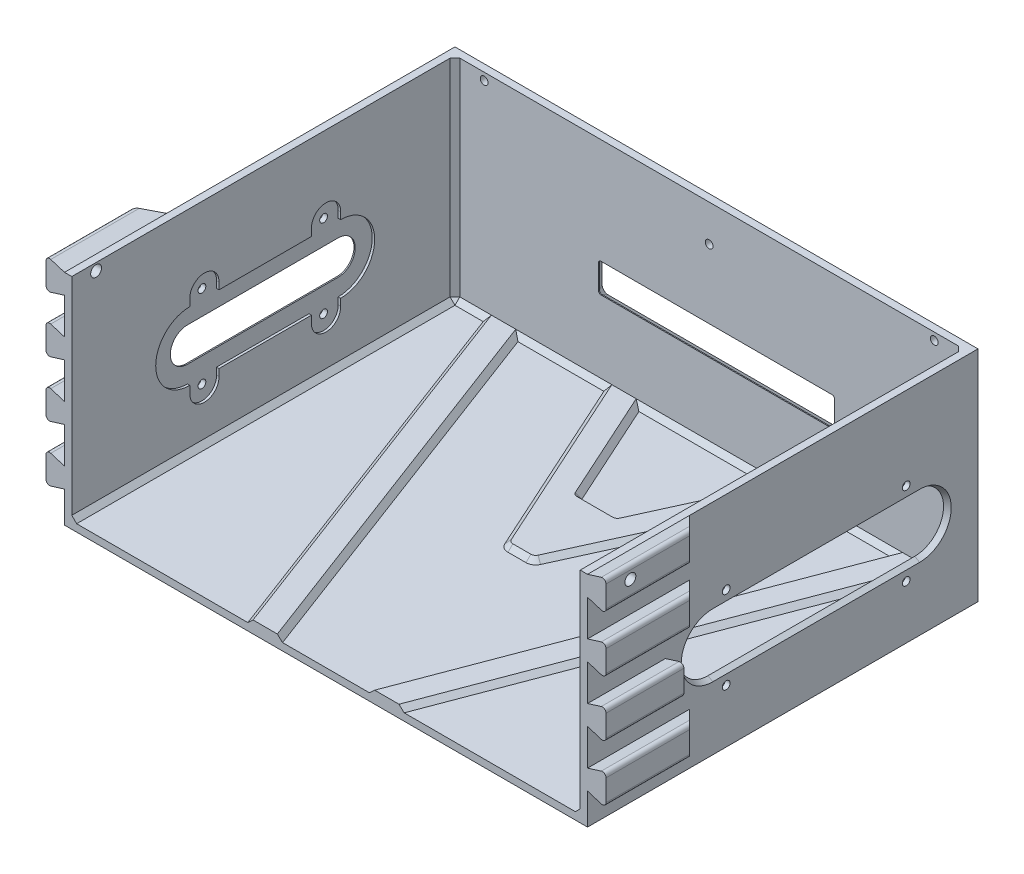
SolidWorks part; units mm, degrees
ref_plane "Płaszczyzna przednia" through (0, 0, 0) normal (0, 0, 1) x (1, 0, 0)
ref_plane "Płaszczyzna górna" through (0, 0, 0) normal (0, 1, 0) x (1, 0, 0)
ref_plane "Płaszczyzna prawa" through (0, 0, 0) normal (1, 0, 0) x (0, 0, -1)
sketch "Szkic1" plane through (0, 0, 0) normal (0, 0, 1) x (1, 0, 0)
  line L1 (0, 0) -> (215, 0)
  line L2 (0, 0) -> (0, 90)
  line L3 (0, 90) -> (215, 90)
  line L4 (215, 0) -> (215, 90)
  dimension "D1" = 90
  dimension "D2" = 215
extrude "Dodanie-wyciągnięcie1" add sketch "Szkic1" along normal blind 3
sketch "Szkic2" plane through (0, 0, 3) normal (0, 0, 1) x (1, 0, 0)
  line L0 (0, 90) -> (0, 0)
  line L1 (0, 0) -> (215, 0)
  line L2 (215, 0) -> (215, 90)
  line L3 (215, 90) -> (212, 90)
  line L4 (215, 90) -> (0, 90) construction
  line L5 (212, 90) -> (212, 3)
  line L6 (212, 3) -> (3, 3)
  line L7 (3, 3) -> (3, 90)
  line L8 (3, 90) -> (0, 90)
  dimension "D1" = 3
  dimension "D2" = 3
  dimension "D3" = 3
extrude "Dodanie-wyciągnięcie2" add sketch "Szkic2" along normal blind 157.5
sketch "Szkic3" plane through (0, 3, 0) normal (0, 1, 0) x (1, 0, 0)
  line L0 (18, -3) -> (77.5, -160.5)
  line L1 (212, -3) -> (3, -3) construction
  line L2 (212, -160.5) -> (3, -160.5) construction
  line L3 (28, -3) -> (87.5, -160.5)
  line L4 (212, -3) -> (3, -3) construction
  line L5 (100.1515, -50) -> (114.8485, -50)
  line L6 (77.5, -160.5) -> (87.5, -160.5)
  line L7 (18, -3) -> (28, -3)
  line L8 (197, -3) -> (137.5, -160.5)
  line L9 (137.5, -160.5) -> (127.5, -160.5)
  line L10 (127.5, -160.5) -> (137.5, -160.5)
  line L11 (127.5, -160.5) -> (187, -3)
  line L12 (187, -3) -> (197, -3)
  line L13 (215, 0) -> (0, 0) construction
  line L14 (67.5, -3) -> (101.9671, -78.8276)
  line L15 (113.0329, -78.8276) -> (147.5, -3)
  line L16 (137.5, -3) -> (116.6693, -48.8276)
  line L17 (98.3307, -48.8276) -> (77.5, -3)
  line L18 (103.7878, -80) -> (111.2122, -80)
  line L19 (67.5, -3) -> (77.5, -3)
  line L20 (137.5, -3) -> (147.5, -3)
  line L21 (107.5, 0) -> (107.5, -100) construction
  arc A0 (114.8485, -50) -> (116.6693, -48.8276) centre (114.8485, -48) ccw
  arc A1 (100.1515, -50) -> (98.3307, -48.8276) centre (100.1515, -48) cw
  arc A2 (111.2122, -80) -> (113.0329, -78.8276) centre (111.2122, -78) ccw
  arc A3 (103.7878, -80) -> (101.9671, -78.8276) centre (103.7878, -78) cw
  point P14 (107.5, 0)
  point P33 (112.5, -80)
  point P36 (102.5, -80)
  point P39 (107.5, -50)
  line M5 (212, -3) -> (3, -3)
  line M7 (3, -160.5) -> (212, -160.5)
  dimension "D16" = 2
  dimension "D1" = 20
  dimension "D2" = 15
  dimension "D3" = 40
  dimension "D4" = 10
  dimension "D5" = 15
  dimension "D6" = 10
  dimension "D7" = 10
  dimension "D8" = 10
  dimension "D9" = 10
  dimension "D10" = 10
  dimension "D11" = 10
  dimension "D12" = 5
  dimension "D13" = 60
  dimension "D14" = 80
  dimension "D15" = 30
extrude "Dodanie-wyciągnięcie3" add sketch "Szkic3" along normal blind 2 contours L3 L0 M5 M7 | L11 L8 M7 M5 | L20 L15 A2 L18 A3 L14 L19 L17 A1 L5 A0 L16 region at (52.75, 3, 81.75) region at (162.25, 3, 81.75)
chamfer "Sfazowanie2" distance 2 angle 45 23 edges at (167.25, 3, 81.75) (212, 46.5, 3) (212, 3, 81.75) (204.5, 3, 3) (57.75, 3, 81.75) (157.25, 3, 81.75) (167.25, 3, 3) (47.75, 3, 3) (47.75, 3, 81.75) (10.5, 3, 3) (3, 3, 81.75) (3, 46.5, 3) (107.5, 3, 3) (84.7335, 3, 40.9138) (102.7051, 3, 79.6815) (107.5, 3, 80) (112.2949, 3, 79.6815) (130.2665, 3, 40.9138) (127.0846, 3, 25.9138) (115.9313, 3, 49.6815) (107.5, 3, 50) (99.0687, 3, 49.6815) (87.9154, 3, 25.9138)
sketch "Szkic4" plane through (0, 0, 3) normal (0, 0, 1) x (1, 0, 0)
  line L0 (184.1065, 3) -> (148.7878, 3) construction
  line L1 (63, 46.7) -> (158, 46.7)
  line L2 (62, 45.7) -> (62, 35.7)
  line L3 (63, 34.7) -> (158, 34.7)
  line L4 (159, 45.7) -> (159, 35.7)
  line L5 (212, 90) -> (212, 5) construction
  arc A0 (158, 46.7) -> (159, 45.7) centre (158, 45.7) cw
  arc A1 (158, 34.7) -> (159, 35.7) centre (158, 35.7) ccw
  arc A2 (62, 35.7) -> (63, 34.7) centre (63, 35.7) ccw
  arc A3 (63, 46.7) -> (62, 45.7) centre (63, 45.7) ccw
  point P12 (159, 34.7)
  point P15 (62, 34.7)
  point P18 (62, 46.7)
  dimension "D5" = 1
  dimension "D1" = 31.7
  dimension "D2" = 53
  dimension "D3" = 12
  dimension "D4" = 97
extrude "Wytnij-wyciągnięcie1" cut sketch "Szkic4" against normal blind 10
sketch "Szkic5" plane through (215, 0, 0) normal (1, 0, 0) x (0, 0, -1)
  line L0 (-109, 39) -> (-24, 39) construction
  line L1 (-109, 50.5) -> (-24, 50.5)
  line L2 (-109, 27.5) -> (-24, 27.5)
  line L3 (-160.5, 0) -> (0, 0) construction
  line L4 (-160.5, 90) -> (0, 90) construction
  line L5 (0, 0) -> (0, 90) construction
  arc A0 (-109, 50.5) -> (-109, 27.5) centre (-109, 39) ccw
  arc A1 (-24, 27.5) -> (-24, 50.5) centre (-24, 39) ccw
  point P2 (-66.5, 39)
  dimension "D4" = 24
  dimension "D1" = 27.5
  dimension "D2" = 39.5
  dimension "D3" = 85
extrude "Wytnij-wyciągnięcie2" cut sketch "Szkic5" against normal blind 10
chamfer "Sfazowanie4" distance 1.5 angle 60 12 edges at (110.5, 46.7, 0) (158.7071, 46.4071, 0) (62.2929, 46.4071, 0) (159, 40.7, 0) (62, 40.7, 0) (158.7071, 34.9929, 0) (62.2929, 34.9929, 0) (110.5, 34.7, 0) (215, 39, 12.5) (215, 50.5, 66.5) (215, 27.5, 66.5) (215, 39, 120.5) first distance on face at (110.5, 40.7, 0) first distance on face at (215, 39, 66.5)
sketch "Szkic6" plane through (215, 0, 0) normal (1, 0, 0) x (0, 0, -1)
  line L0 (-24, 39) -> (-109, 39) construction
  line L1 (-24, 24) -> (-109, 24)
  line L2 (-24, 54) -> (-109, 54)
  line L3 (-66.5, 39) -> (-66.5, 64.1072) construction
  line L4 (-109, 54) -> (-98, 54)
  line L5 (-109, 54) -> (-109, 56)
  line L7 (-98, 54) -> (-98, 56)
  line L8 (-66.5, 39) -> (-84.4826, 39) construction
  line L9 (-35, 54) -> (-35, 56)
  line L10 (-24, 54) -> (-24, 56)
  line L11 (-24, 54) -> (-35, 54)
  line L12 (-109, 54) -> (-109, 56)
  line L13 (-98, 54) -> (-98, 56)
  line L14 (-35, 54) -> (-35, 56)
  line L15 (-24, 54) -> (-24, 56)
  line L16 (-109, 54) -> (-109, 56)
  line L17 (-98, 54) -> (-98, 56)
  line L18 (-35, 54) -> (-35, 56)
  line L19 (-24, 54) -> (-24, 56)
  line L20 (-109, 54) -> (-109, 56)
  line L21 (-98, 54) -> (-98, 56)
  line L22 (-35, 54) -> (-35, 56)
  line L23 (-24, 54) -> (-24, 56)
  line L24 (-66.5, 39) -> (-132.3508, 39) construction
  line L25 (-109, 54) -> (-109, 56)
  line L26 (-98, 54) -> (-98, 56)
  line L27 (-35, 54) -> (-35, 56)
  line L28 (-24, 54) -> (-24, 56)
  line L29 (-109, 54) -> (-109, 56)
  line L30 (-98, 54) -> (-98, 56)
  line L31 (-35, 54) -> (-35, 56)
  line L32 (-24, 54) -> (-24, 56)
  line L33 (-109, 54) -> (-109, 56)
  line L34 (-98, 54) -> (-98, 56)
  line L35 (-35, 54) -> (-35, 56)
  line L36 (-24, 54) -> (-24, 56)
  line L37 (-109, 54) -> (-109, 56)
  line L38 (-98, 54) -> (-98, 56)
  line L39 (-35, 54) -> (-35, 56)
  line L40 (-24, 54) -> (-24, 56)
  line L41 (-24, 24) -> (-24, 22)
  line L42 (-35, 24) -> (-35, 22)
  line L43 (-109, 24) -> (-109, 22)
  line L44 (-98, 24) -> (-98, 22)
  arc A0 (-24, 24) -> (-24, 54) centre (-24, 39) ccw
  arc A1 (-109, 54) -> (-109, 24) centre (-109, 39) ccw
  arc A2 (-98, 56) -> (-109, 56) centre (-103.5, 56) ccw
  arc A3 (-35, 56) -> (-24, 56) centre (-29.5, 56) cw
  arc A4 (-98, 56) -> (-109, 56) centre (-103.5, 56) ccw
  arc A5 (-35, 56) -> (-24, 56) centre (-29.5, 56) cw
  arc A6 (-98, 56) -> (-109, 56) centre (-103.5, 56) ccw
  arc A7 (-35, 56) -> (-24, 56) centre (-29.5, 56) cw
  arc A8 (-98, 56) -> (-109, 56) centre (-103.5, 56) ccw
  arc A9 (-35, 56) -> (-24, 56) centre (-29.5, 56) cw
  arc A10 (-98, 56) -> (-109, 56) centre (-103.5, 56) ccw
  arc A11 (-35, 56) -> (-24, 56) centre (-29.5, 56) cw
  arc A12 (-98, 56) -> (-109, 56) centre (-103.5, 56) ccw
  arc A13 (-35, 56) -> (-24, 56) centre (-29.5, 56) cw
  arc A14 (-98, 56) -> (-109, 56) centre (-103.5, 56) ccw
  arc A15 (-35, 56) -> (-24, 56) centre (-29.5, 56) cw
  arc A16 (-98, 56) -> (-109, 56) centre (-103.5, 56) ccw
  arc A17 (-35, 56) -> (-24, 56) centre (-29.5, 56) cw
  arc A18 (-35, 22) -> (-24, 22) centre (-29.5, 22) ccw
  arc A19 (-98, 22) -> (-109, 22) centre (-103.5, 22) cw
  point P4 (-66.5, 39)
  line M16 (-109, 52) -> (-24, 52)
  arc M17 (-24, 52) -> (-24, 26) centre (-24, 39) cw
  line M18 (-24, 26) -> (-109, 26)
  arc M19 (-109, 26) -> (-109, 52) centre (-109, 39) cw
  dimension "D1" = 15
  dimension "D3" = 2
  dimension "D2" = 11
  dimension "D4" = 2
extrude "Wytnij-wyciągnięcie3" cut sketch "Szkic6" along normal blind 1 from surface contours A19 L44 L1 L43 | L42 A18 L41 L1 | L2 A1 L1 A0 M19 M16 M17 M18 | A3 L9 L2 L10 | L7 A2 L5 L2 | M16 M19 M18 M17 region at (215, 20.7209, 29.5) region at (215, 25.1885, 29.5) region at (215, 57.2791, 29.5) region at (215, 20.7209, 103.5) region at (215, 57.2791, 103.5) region at (215, 39, 66.5) starting at face at (212, 39, 66.5)
sketch "Szkic7" plane through (215, 0, 0) normal (1, 0, 0) x (0, 0, -1)
  line L0 (-66.5, 39) -> (-66.5, 73.0963) construction
  line L1 (-66.5, 39) -> (-141.7626, 39) construction
  circle A0 centre (-103.5, 56) radius 1.6
  circle A1 centre (-29.5, 56) radius 1.6
  circle A2 centre (-29.5, 22) radius 1.6
  circle A3 centre (-103.5, 22) radius 1.6
  dimension "D1" = 3.2
extrude "Wytnij-wyciągnięcie4" cut sketch "Szkic7" against normal blind 3
sketch "Szkic10" plane through (0, 0, 160.5) normal (0, 0, 1) x (1, 0, 0)
  line L0 (222.6, 93.3093) -> (222.6, 6.3093) construction
  line L1 (215, 0) -> (215, 90) construction
  line L2 (215, 81.84) -> (215, 90)
  line L3 (215, 81.84) -> (220.6526, 80.0735)
  line L4 (215, 90) -> (220.6526, 91.7665)
  line L5 (222.6, 90.3348) -> (222.6, 81.5052)
  line L6 (107.5, 90) -> (107.5, 114.4452) construction
  line L7 (210, 90) -> (5, 90) construction
  line L36 (215, 58.84) -> (215, 67)
  line L37 (215, 58.84) -> (220.6526, 57.0735)
  line L38 (215, 67) -> (220.6526, 68.7665)
  line L39 (222.6, 67.3348) -> (222.6, 58.5052)
  line L40 (215, 35.84) -> (215, 44)
  line L41 (215, 35.84) -> (220.6526, 34.0735)
  line L42 (215, 44) -> (220.6526, 45.7665)
  line L43 (222.6, 44.3348) -> (222.6, 35.5052)
  line L44 (215, 12.84) -> (215, 21)
  line L45 (215, 12.84) -> (220.6526, 11.0735)
  line L46 (215, 21) -> (220.6526, 22.7665)
  line L47 (222.6, 21.3348) -> (222.6, 12.5052)
  line L48 (-7.6, 21.3348) -> (-7.6, 12.5052)
  line L49 (0, 21) -> (-5.6526, 22.7665)
  line L50 (0, 12.84) -> (-5.6526, 11.0735)
  line L51 (0, 12.84) -> (0, 21)
  line L52 (-7.6, 44.3348) -> (-7.6, 35.5052)
  line L53 (0, 44) -> (-5.6526, 45.7665)
  line L54 (0, 35.84) -> (-5.6526, 34.0735)
  line L55 (0, 35.84) -> (0, 44)
  line L56 (-7.6, 67.3348) -> (-7.6, 58.5052)
  line L57 (0, 67) -> (-5.6526, 68.7665)
  line L58 (0, 58.84) -> (-5.6526, 57.0735)
  line L59 (0, 58.84) -> (0, 67)
  line L60 (-7.6, 90.3348) -> (-7.6, 81.5052)
  line L61 (0, 90) -> (-5.6526, 91.7665)
  line L62 (0, 81.84) -> (-5.6526, 80.0735)
  line L63 (0, 81.84) -> (0, 90)
  arc A0 (220.6526, 80.0735) -> (222.6, 81.5052) centre (221.1, 81.5052) ccw
  arc A1 (220.6526, 91.7665) -> (222.6, 90.3348) centre (221.1, 90.3348) cw
  arc A16 (220.6526, 57.0735) -> (222.6, 58.5052) centre (221.1, 58.5052) ccw
  arc A17 (220.6526, 68.7665) -> (222.6, 67.3348) centre (221.1, 67.3348) cw
  arc A18 (220.6526, 34.0735) -> (222.6, 35.5052) centre (221.1, 35.5052) ccw
  arc A19 (220.6526, 45.7665) -> (222.6, 44.3348) centre (221.1, 44.3348) cw
  arc A20 (220.6526, 11.0735) -> (222.6, 12.5052) centre (221.1, 12.5052) ccw
  arc A21 (220.6526, 22.7665) -> (222.6, 21.3348) centre (221.1, 21.3348) cw
  arc A22 (-5.6526, 22.7665) -> (-7.6, 21.3348) centre (-6.1, 21.3348) ccw
  arc A23 (-5.6526, 11.0735) -> (-7.6, 12.5052) centre (-6.1, 12.5052) cw
  arc A24 (-5.6526, 45.7665) -> (-7.6, 44.3348) centre (-6.1, 44.3348) ccw
  arc A25 (-5.6526, 34.0735) -> (-7.6, 35.5052) centre (-6.1, 35.5052) cw
  arc A26 (-5.6526, 68.7665) -> (-7.6, 67.3348) centre (-6.1, 67.3348) ccw
  arc A27 (-5.6526, 57.0735) -> (-7.6, 58.5052) centre (-6.1, 58.5052) cw
  arc A28 (-5.6526, 91.7665) -> (-7.6, 90.3348) centre (-6.1, 90.3348) ccw
  arc A29 (-5.6526, 80.0735) -> (-7.6, 81.5052) centre (-6.1, 81.5052) cw
  point P11 (222.6, 79.4649)
  point P14 (222.6, 92.3751)
  point P74 (-7.6, 92.3751)
  point P75 (-7.6, 79.4649)
  dimension "D5" = 1.5
  dimension "D1" = 7.6
  dimension "D2" = 8.16
  dimension "D3" = 4
  dimension "D4" = 34.71
extrude "Dodanie-wyciągnięcie6" add sketch "Szkic10" against normal blind 32
chamfer "Sfazowanie5" distance 10 angle 45 6 edges at (215, 85.92, 128.5) (215, 16.92, 128.5) (215, 62.92, 128.5) (0, 85.92, 128.5) (0, 62.92, 128.5) (0, 16.92, 128.5)
sketch "Szkic11" plane through (0, 0, 0) normal (-1, 0, 0) x (0, 0, 1)
  line L0 (112, 41) -> (50, 41) construction
  line L1 (112, 34) -> (50, 34)
  line L2 (112, 48) -> (50, 48)
  line L3 (118.5, 90) -> (0, 90) construction
  line L4 (0, 90) -> (0, 0) construction
  arc A0 (112, 34) -> (112, 48) centre (112, 41) ccw
  arc A1 (50, 48) -> (50, 34) centre (50, 41) ccw
  point P2 (81, 41)
  dimension "D3" = 7
  dimension "D1" = 42
  dimension "D2" = 62
  dimension "D4" = 50
extrude "Wytnij-wyciągnięcie5" cut sketch "Szkic11" against normal blind 10
sketch "Szkic12" plane through (0, 0, 0) normal (-1, 0, 0) x (0, 0, 1)
  line L0 (112, 41) -> (50, 41) construction
  line L1 (112, 27) -> (50, 27)
  line L2 (112, 55) -> (50, 55)
  line L3 (102.8467, 55) -> (100, 55)
  line L4 (112, 55) -> (102.8467, 55)
  line L5 (112, 55) -> (112, 57.7839)
  line L7 (100, 55) -> (100, 57.7839)
  line L8 (81, 41) -> (81, 27) construction
  line L9 (62, 55) -> (62, 57.7839)
  line L10 (50, 55) -> (50, 57.7839)
  line L11 (50, 55) -> (59.1533, 55)
  line L12 (59.1533, 55) -> (62, 55)
  line L13 (81, 41) -> (24.5654, 41) construction
  line L14 (59.1533, 27) -> (62, 27)
  line L15 (50, 27) -> (59.1533, 27)
  line L16 (50, 27) -> (50, 24.2161)
  line L17 (62, 27) -> (62, 24.2161)
  line L18 (100, 27) -> (100, 24.2161)
  line L19 (112, 27) -> (112, 24.2161)
  line L20 (112, 27) -> (102.8467, 27)
  line L21 (102.8467, 27) -> (100, 27)
  arc A0 (112, 27) -> (112, 55) centre (112, 41) ccw
  arc A1 (50, 55) -> (50, 27) centre (50, 41) ccw
  arc A2 (112, 57.7839) -> (100, 57.7839) centre (106, 58) ccw
  arc A3 (50, 57.7839) -> (62, 57.7839) centre (56, 58) cw
  arc A4 (50, 24.2161) -> (62, 24.2161) centre (56, 24) ccw
  arc A5 (112, 24.2161) -> (100, 24.2161) centre (106, 24) cw
  point P4 (81, 41)
  line M18 (50, 48) -> (112, 48)
  arc M19 (112, 48) -> (112, 34) centre (112, 41) cw
  line M20 (112, 34) -> (50, 34)
  arc M21 (50, 34) -> (50, 48) centre (50, 41) cw
  dimension "D2" = 14
  dimension "D1" = 12
  dimension "D3" = 34
extrude "Wytnij-wyciągnięcie6" cut sketch "Szkic12" along normal blind 1 from surface contours L2 A1 L1 A0 M21 M18 M19 M20 | L5 A2 L7 L2 | A5 L19 L1 L18 | L16 A4 L17 L1 | A3 L10 L2 L9 region at (0, 23.0253, 106) region at (0, 27.9425, 107.4233) region at (0, 58.9747, 106) region at (0, 23.0253, 56) region at (0, 58.9747, 56) starting at face at (3, 41, 81)
sketch "Szkic13" plane through (0, 0, 0) normal (-1, 0, 0) x (0, 0, 1)
  line L0 (81, 41) -> (81, 27) construction
  line L1 (112, 41) -> (50, 41) construction
  line L4 (24.5654, 41) -> (81, 41) construction
  circle A0 centre (106, 58) radius 1.6
  circle A1 centre (106, 24) radius 1.6
  circle A2 centre (56, 24) radius 1.6
  circle A3 centre (56, 58) radius 1.6
  dimension "D1" = 3.2
extrude "Wytnij-wyciągnięcie7" cut sketch "Szkic13" against normal blind 3
chamfer "Sfazowanie8" distance 1.5 angle 60 4 edges at (0, 48, 81) (0, 41, 43) (0, 34, 81) (0, 41, 119) first distance on face at (1, 48, 81) first distance on face at (1, 41, 46.5) first distance on face at (1, 34, 81) first distance on face at (1, 41, 115.5)
sketch "Szkic14" plane through (0, 0, 0) normal (-1, 0, 0) x (0, 0, 1)
  line L1 (118.5, 90) -> (0, 90) construction
  line L2 (160.5, 90.3348) -> (160.5, 81.5052) construction
  circle A0 centre (150.5, 87) radius 2.25
  dimension "D2" = 4.5
  dimension "D1" = 10
  dimension "D3" = 3
extrude "Wytnij-wyciągnięcie8" cut sketch "Szkic14" against normal through all and the other way blind 10
sketch "Szkic15" plane through (0, 0, 0) normal (0, 0, -1) x (-1, 0, 0)
  line L0 (0, 90) -> (0, 0) construction
  line L1 (-215, 90) -> (0, 90) construction
  circle A0 centre (-15, 87) radius 1.6
  dimension "D1" = 3.2
  dimension "D2" = 15
  dimension "D3" = 3
extrude "Wytnij-wyciągnięcie9" cut sketch "Szkic15" against normal through all contours A0
ref_plane "Płaszczyzna1" through (107.5, 0, 0) normal (-1, 0, 0) x (0, 0, 1)
mirror "Lustro1" about plane through (107.5, 0, 0) normal (-1, 0, 0) of "Wytnij-wyciągnięcie9"
sketch "Szkic16" plane through (0, 0, 0) normal (0, 0, -1) x (-1, 0, 0)
  line L0 (-107.5, -47.85) -> (-107.5, 47.85) construction
  line L1 (-215, 90) -> (0, 90) construction
  circle A0 centre (-107.5, 75) radius 1.6
  dimension "D1" = 3.2
  dimension "D2" = 15
extrude "Wytnij-wyciągnięcie10" cut sketch "Szkic16" against normal blind 35
